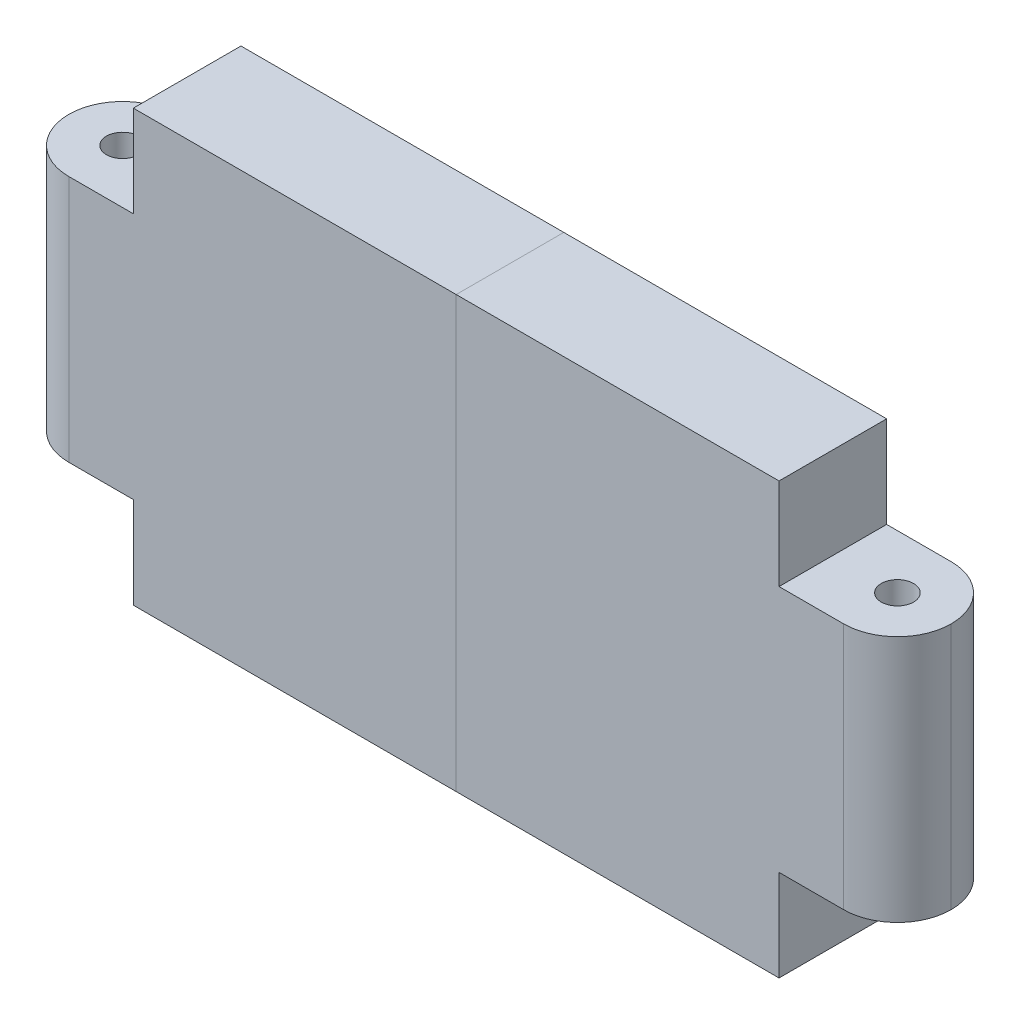
SolidWorks part; units mm, degrees
ref_plane "前视基准面" through (0, 0, 0) normal (0, 0, 1) x (1, 0, 0)
ref_plane "上视基准面" through (0, 0, 0) normal (0, 1, 0) x (1, 0, 0)
ref_plane "右视基准面" through (0, 0, 0) normal (1, 0, 0) x (0, 0, -1)
other "Configuration Table"
sketch "草图1" plane through (0, 0, 0) normal (0, 0, 1) x (1, 0, 0)
  line L1 (-30, 20) -> (30, 20)
  line L2 (-30, 20) -> (-30, -20)
  line L3 (-30, -20) -> (30, -20)
  line L4 (30, 20) -> (30, -20)
  line L5 (-30, 20) -> (30, -20) construction
  line L6 (-30, -20) -> (30, 20) construction
  point P0 (0, 0)
  dimension "D1" = 60
  dimension "D2" = 40
extrude "凸台-拉伸1" add sketch "草图1" along normal blind 10
sketch "草图2" plane through (-30, 0, 0) normal (-1, 0, 0) x (0, 0, 1)
  line L0 (0, 20) -> (0, -20) construction
  line L1 (0, 11.5) -> (10, 11.5)
  line L2 (0, 11.5) -> (0, -11.5)
  line L3 (0, -11.5) -> (10, -11.5)
  line L4 (10, 11.5) -> (10, -11.5)
  line L5 (10, 20) -> (10, -20) construction
  dimension "D1" = 23
  dimension "D2" = 11.5
extrude "凸台-拉伸2" add sketch "草图2" along normal blind 11
sketch "草图3" plane through (0, 11.5, 0) normal (0, 1, 0) x (1, 0, 0)
  line L0 (-41, -10) -> (-41, 0) construction
  line L1 (-41, 0) -> (-30, 0) construction
  circle A0 centre (-36, -5) radius 1.5
  dimension "D1" = 3
  dimension "D2" = 5
  dimension "D3" = 5
extrude "切除-拉伸1" cut sketch "草图3" against normal blind 30
mirror "镜向1" about plane through (0, 0, 0) normal (1, 0, 0) of "切除-拉伸1", "凸台-拉伸2"
fillet "圆角1" radius 5 4 edges at (41, 0, 0) (41, 0, 10) (-41, 0, 0) (-41, 0, 10)
ref_plane "基准面1" through (0, 0, 0) normal (-1, 0, 0) x (0, 0, 1)
split "分割1" trim tools "基准面1" bodies to split 109 resulting bodies 110 111
